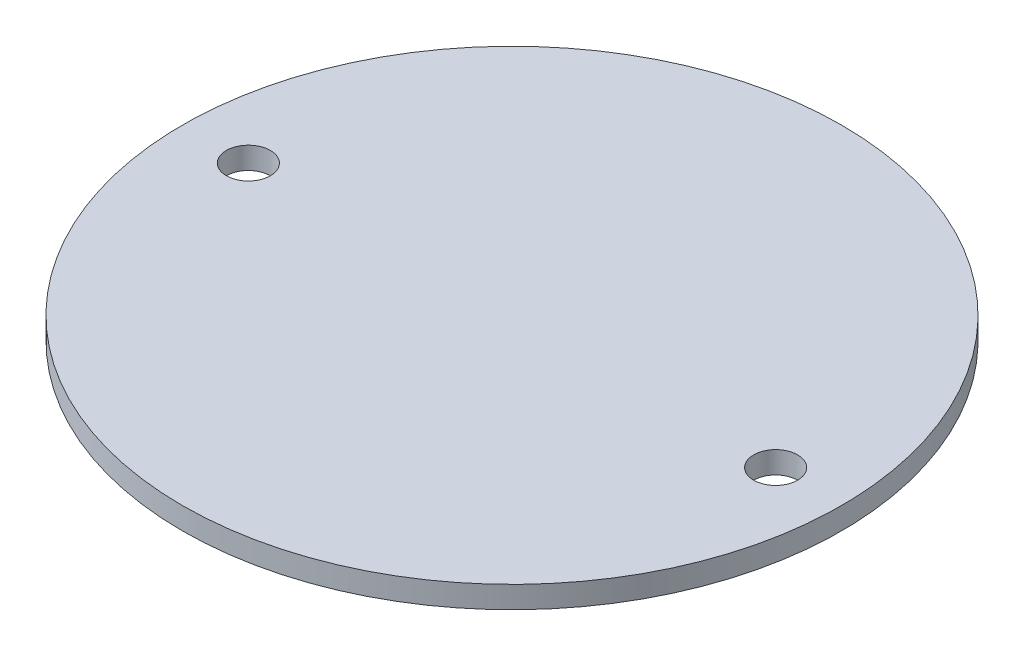
SolidWorks part; units mm, degrees
material "A-Glass Fiber"
ref_plane "Front Plane" through (0, 0, 0) normal (0, 0, 1) x (1, 0, 0)
ref_plane "Top Plane" through (0, 0, 0) normal (0, 1, 0) x (1, 0, 0)
ref_plane "Right Plane" through (0, 0, 0) normal (1, 0, 0) x (0, 0, -1)
sketch "Sketch1" plane through (0, 0, 0) normal (0, 1, 0) x (1, 0, 0)
  circle A0 centre (0, 0) radius 47.625
  dimension "D1" = 95.25
extrude "Boss-Extrude1" add sketch "Sketch1" along normal blind 3.175
extrude "Cut-Extrude1" cut sketch "Sketch2" against normal blind 263.398
sketch "Sketch2" plane through (-55.0397, 231.775, -116.0884) normal (0, 1, 0) x (-1, 0, 0)
  circle A0 centre (-93.1397, 116.0884) radius 3.175
  circle A1 centre (-16.9397, 116.0884) radius 3.175
  point P4 (0, 0)
